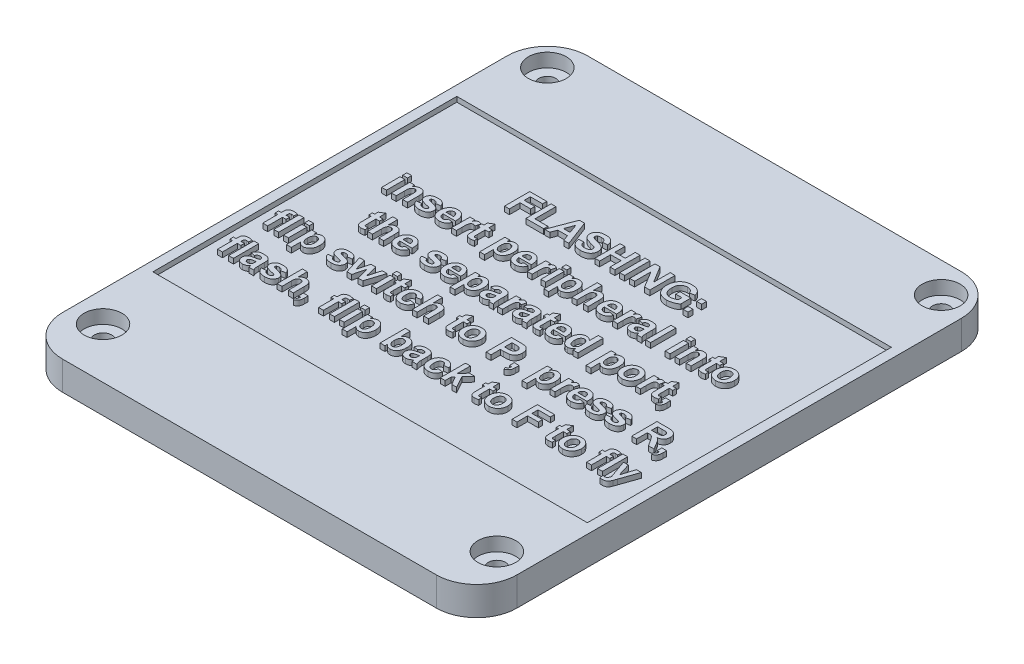
SolidWorks part; units mm, degrees
ref_plane "Спереди" through (0, 0, 0) normal (0, 0, 1) x (1, 0, 0)
ref_plane "Сверху" through (0, 0, 0) normal (0, 1, 0) x (1, 0, 0)
ref_plane "Справа" through (0, 0, 0) normal (1, 0, 0) x (0, 0, -1)
sketch "Sketch1" plane through (0, 0, 0) normal (0, 1, 0) x (1, 0, 0)
  line L1 (45, -50) -> (-45, -50)
  line L2 (45, -50) -> (45, 50)
  line L3 (45, 50) -> (-45, 50)
  line L4 (-45, -50) -> (-45, 50)
  line L5 (45, -50) -> (-45, 50) construction
  line L6 (45, 50) -> (-45, -50) construction
  point P0 (0, 0)
  dimension "D1" = 90
  dimension "D2" = 100
extrude "Boss-Extrude1" add sketch "Sketch1" along normal blind 3
sketch "Sketch2" plane through (0, 3, 0) normal (0, 1, 0) x (1, 0, 0)
  line L0 (-45, 50) -> (-45, -50) construction
  line L1 (39, -44) -> (-39, -44) construction
  line L2 (39, -44) -> (39, 44) construction
  line L3 (39, 44) -> (-39, 44) construction
  line L4 (-39, -44) -> (-39, 44) construction
  line L5 (39, -44) -> (-39, 44) construction
  line L6 (39, 44) -> (-39, -44) construction
  line L7 (45, 50) -> (-45, 50) construction
  circle A0 centre (-39, 44) radius 1.7
  circle A1 centre (39, 44) radius 1.7
  circle A2 centre (39, -44) radius 1.7
  circle A3 centre (-39, -44) radius 1.7
  point P0 (0, 0)
  dimension "D3" = 3.4
  dimension "D1" = 6
  dimension "D2" = 6
extrude "Cut-Extrude1" cut sketch "Sketch2" against normal through all
sketch "Sketch4" plane through (0, 0, 0) normal (0, -1, 0) x (1, 0, 0)
  line L0 (-45, -50) -> (-45, 50) construction
  line L1 (41.6, 46.6) -> (-38.6, 46.6)
  line L2 (41.6, 46.6) -> (41.6, -46.6)
  line L3 (41.6, -46.6) -> (-38.6, -46.6)
  line L4 (-38.6, 46.6) -> (-38.6, -46.6)
  line L5 (-45, 50) -> (45, 50) construction
  line L6 (45, 50) -> (45, -50) construction
  line L7 (45, -50) -> (-45, -50) construction
  line L9 (38.6, 43.6) -> (-35.6, 43.6)
  line L10 (38.6, 43.6) -> (38.6, -43.6)
  line L11 (38.6, -43.6) -> (-35.6, -43.6)
  line L12 (-35.6, 43.6) -> (-35.6, -43.6)
  point P0 (0, 0)
  point P10 (0, 0)
  dimension "D1" = 6.4
  dimension "D2" = 3.4
  dimension "D3" = 3
  dimension "D4" = 3
  dimension "D5" = 3
  dimension "D6" = 3.4
  dimension "D7" = 3
  dimension "D8" = 3.4
extrude "Boss-Extrude2" add sketch "Sketch4" along normal blind 2
sketch "Sketch6" plane through (0, 3, 0) normal (0, 1, 0) x (1, 0, 0)
  line L0 (45, -50) -> (45, 50) construction
  circle A0 centre (-39, 44) radius 6
  circle A1 centre (-39, -44) radius 6
  circle A2 centre (39, -44) radius 6
  circle A3 centre (39, 44) radius 6
extrude "Cut-Extrude5" cut sketch "Sketch6" against normal through all from offset 3 offset against normal yes
sketch "Sketch7" plane through (0, 0, 50) normal (0, 0, 1) x (1, 0, 0)
  line L0 (-45, 3) -> (-45, 0)
  line L1 (-45, 0) -> (45, 0)
  line L2 (45, 0) -> (45, 3)
  line L3 (45, 3) -> (-45, 3)
extrude "Boss-Extrude3" add sketch "Sketch7" along normal blind 4
sketch "Sketch8" plane through (0, 3, 0) normal (0, 1, 0) x (1, 0, 0)
  line L0 (-45, -50) -> (-45, -54)
  line L1 (-45, -54) -> (45, -54)
  line L2 (45, -50) -> (45, 50)
  line L3 (45, 50) -> (-45, 50)
  line L4 (-45, -50) -> (-45, 50)
  line L5 (45, -50) -> (-45, 50) construction
  line L6 (45, 50) -> (-45, -50) construction
  line L7 (45, -54) -> (45, -50)
  circle A1 centre (-39, 44) radius 3.75
  circle A3 centre (39, 44) radius 3.75
  circle A6 centre (-39, -44) radius 3.75
  circle A7 centre (39, -44) radius 3.75
  point P0 (0, 0)
  dimension "D1" = 7.5
extrude "Boss-Extrude4" add sketch "Sketch8" along normal blind 2.7
fillet "Fillet1" radius 8 4 edges at (-45, 2.85, -50) (-45, 2.85, 54) (45, 2.85, 54) (45, 2.85, -50)
sketch "Sketch10" plane through (0, 5.7, 0) normal (0, 1, 0) x (1, 0, 0)
  line L1 (43.0324, -30.0991) -> (-43.0324, -30.0991)
  line L2 (43.0324, -30.0991) -> (43.0324, 30.0991)
  line L3 (43.0324, 30.0991) -> (-43.0324, 30.0991)
  line L4 (-43.0324, -30.0991) -> (-43.0324, 30.0991)
  line L5 (43.0324, -30.0991) -> (-43.0324, 30.0991) construction
  line L6 (43.0324, 30.0991) -> (-43.0324, -30.0991) construction
  point P0 (0, 0)
extrude "Cut-Extrude7" cut sketch "Sketch10" against normal blind 1
sketch "Sketch9" plane through (0, 4.7, 0) normal (0, 1, 0) x (1, 0, 0)
  line L0 (-45, 16) -> (45, 16) construction
  line L1 (-45, 42) -> (-45, -46) construction
  line L2 (45, -46) -> (45, 42) construction
  text T0 "<b>             FLASHING: </b>\r\n<b>     insert peripheral into</b>\r\n<b>       the separated port, </b>\r\n<b>  flip switch to P, press R, </b>\r\n<b>  flash, flip back to F to fly</b>" font "Arial" height 5
  dimension "D1" = 26
extrude "Boss-Extrude5" add sketch "Sketch9" along normal blind 1
